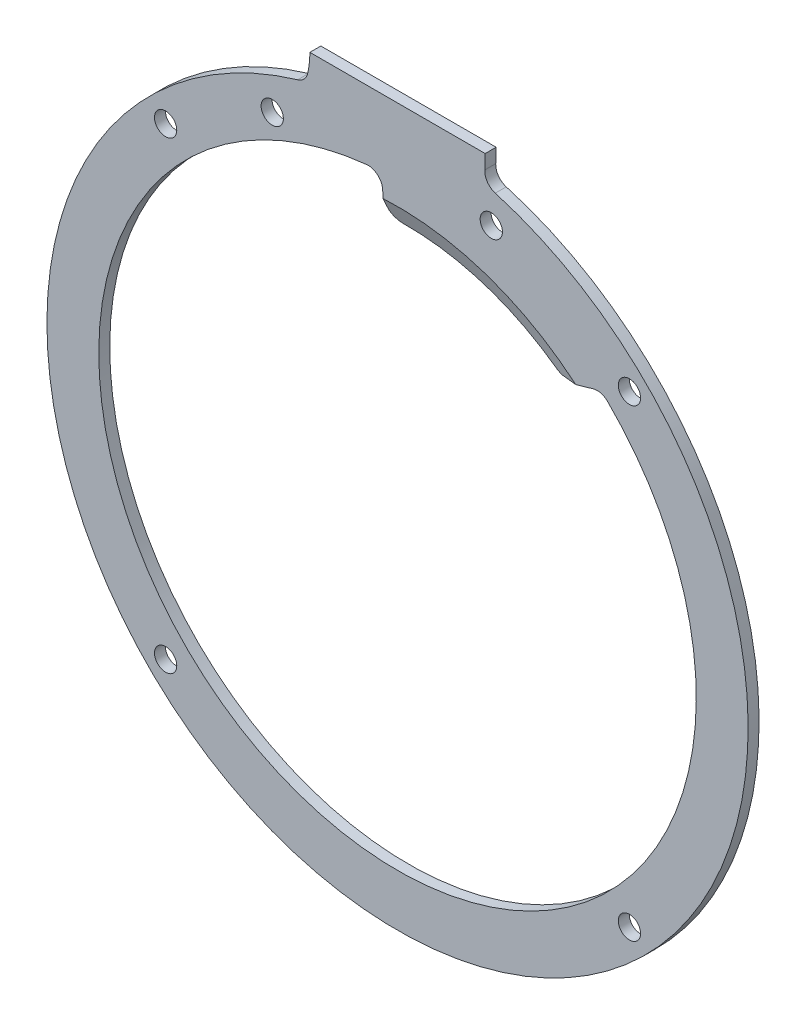
SolidWorks part; units mm, degrees
material "Thornel Mat VMA"
ref_plane "前视基准面" through (0, 0, 0) normal (0, 0, 1) x (1, 0, 0)
ref_plane "上视基准面" through (0, 0, 0) normal (0, 1, 0) x (1, 0, 0)
ref_plane "右视基准面" through (0, 0, 0) normal (1, 0, 0) x (0, 0, -1)
sketch "草图1" plane through (0, 0, 0) normal (0, 0, 1) x (1, 0, 0)
  line L0 (0, 0) -> (0, 50.1) construction
  line L1 (0, 50.1) -> (0, 73.1) construction
  line L2 (-35.5, 73.1) -> (35.5, 73.1) construction
  line L3 (-12, 50.1) -> (12, 50.1)
  line L4 (0, 0) -> (12.8351, 41.9818) construction
  line L5 (0, 0) -> (-17.1531, 40.4102) construction
  circle A0 centre (0, 0) radius 19.04 construction
  circle A1 centre (0, 0) radius 40.9
  circle A2 centre (0, 0) radius 21 construction
  circle A3 centre (-14.8492, 14.8492) radius 1.525 construction
  circle A4 centre (14.8492, 14.8492) radius 1.525 construction
  circle A5 centre (14.8492, -14.8492) radius 1.525 construction
  circle A6 centre (-14.8492, -14.8492) radius 1.525 construction
  circle A7 centre (0, 0) radius 46.4 construction
  circle A8 centre (-35.5, 73.1) radius 30 construction
  circle A9 centre (35.5, 73.1) radius 30 construction
  arc A10 (0, 50.1) -> (-6.8598, 33.3008) centre (-24, 50.1) cw construction
  circle A11 centre (0, 0) radius 34 construction
  circle A12 centre (-1.2412, 42.4819) radius 8.5 construction
  circle A13 centre (0, 59.4365) radius 8.5 construction
  arc A15 (-13.6688, 46.0127) -> (13.3851, 46.096) centre (0, 0) ccw
  arc A18 (-12, 50.1) -> (-12.286, 47.4958) centre (-24, 50.1) cw
  arc A19 (12, 50.1) -> (11.9459, 48.1263) centre (-24, 50.1) cw
  arc A20 (-12.286, 47.4958) -> (-13.6688, 46.0127) centre (-14.2383, 47.9298) cw
  arc A21 (11.9459, 48.1263) -> (13.3851, 46.096) centre (13.9428, 48.0166) ccw
  circle A22 centre (-17.1531, 40.4102) radius 1.525
  circle A23 centre (12.8351, 41.9818) radius 1.525
  point P17 (0, 0)
  dimension "D2" = 38.08
  dimension "D3" = 81.8
  dimension "D4" = 42
  dimension "D6" = 3.05
  dimension "D8" = 60
  dimension "D10" = 24
  dimension "D11" = 68
  dimension "D12" = 17
  dimension "D13" = 92.8
  dimension "D14" = 96
  dimension "D16" = 2
  dimension "D17" = 3.05
  dimension "D1" = 50.1
  dimension "D7" = 71
  dimension "D9" = 23
  dimension "D15" = 24
  dimension "D18" = 43.9
  dimension "D19" = 17
  dimension "D20" = 40
  dimension "D5" = 4
extrude "凸台-拉伸1" add sketch "草图1" along normal blind 1.5
sketch "草图2" plane through (0, 0, 1.5) normal (0, 0, 1) x (1, 0, 0)
  line L0 (-2.1405, 40.8439) -> (-1.9086, 36.4192)
  line L1 (-1.8318, 34.952) -> (0, 0) construction
  line L3 (27.8937, 29.9124) -> (20.0488, 37.2278)
  line L4 (8.5713, 41.4053) -> (-2.1405, 40.8439)
  line L5 (0, 0) -> (0, 40.9) construction
  line L6 (27.8937, 29.9124) -> (21.7732, 28.1559)
  line L7 (21.0635, 27.9522) -> (0, 0) construction
  line L8 (27.8937, 29.9124) -> (0, 0) construction
  line L9 (8.5713, 41.4053) -> (20.0488, 37.2278)
  circle A0 centre (0, 0) radius 40.9 construction
  circle A1 centre (0, 0) radius 35 construction
  arc A2 (-1.9086, 36.4192) -> (-0.3938, 34.9978) centre (-0.4107, 36.4977) ccw
  arc A3 (-0.3938, 34.9978) -> (20.4817, 28.3814) centre (0, 0) cw
  arc A4 (20.4817, 28.3814) -> (21.7732, 28.1559) centre (21.3594, 29.5977) ccw
  circle A5 centre (12.8351, 41.9818) radius 1.525 construction
  dimension "D1" = 70
  dimension "D3" = 1.5
  dimension "D6" = 1.5
  dimension "D7" = 2
  dimension "D2" = 3
  dimension "D4" = 6
  dimension "D5" = 40
extrude "凸台-拉伸2" add sketch "草图2" against normal up to surface (1.5 mm away) up to face at (-15.6281, 40.4102, 0)
fillet "圆角1" radius 2 2 edges at (-2.1405, 40.8439, 0.75) (27.8937, 29.9124, 0.75)
sketch "草图3" plane through (0, 0, 1.5) normal (0, 0, 1) x (1, 0, 0)
  circle A0 centre (0, 0) radius 44.9 construction
  circle A1 centre (-31.7491, 31.7491) radius 1.525
  circle A2 centre (31.7491, 31.7491) radius 1.525
  circle A3 centre (31.7491, -31.7491) radius 1.525
  circle A4 centre (-31.7491, -31.7491) radius 1.525
  point P15 (0, 0)
  dimension "D2" = 3.05
  dimension "D3" = 89.8
  dimension "D1" = 4
extrude "切除-拉伸1" cut sketch "草图3" against normal blind 10
chamfer "倒角1" distance 1.2 angle 67 1 edges at (10.5747, 33.3643, 1.5) tangent propagation no first distance on face at (10.3093, 32.5269, 0.75)
